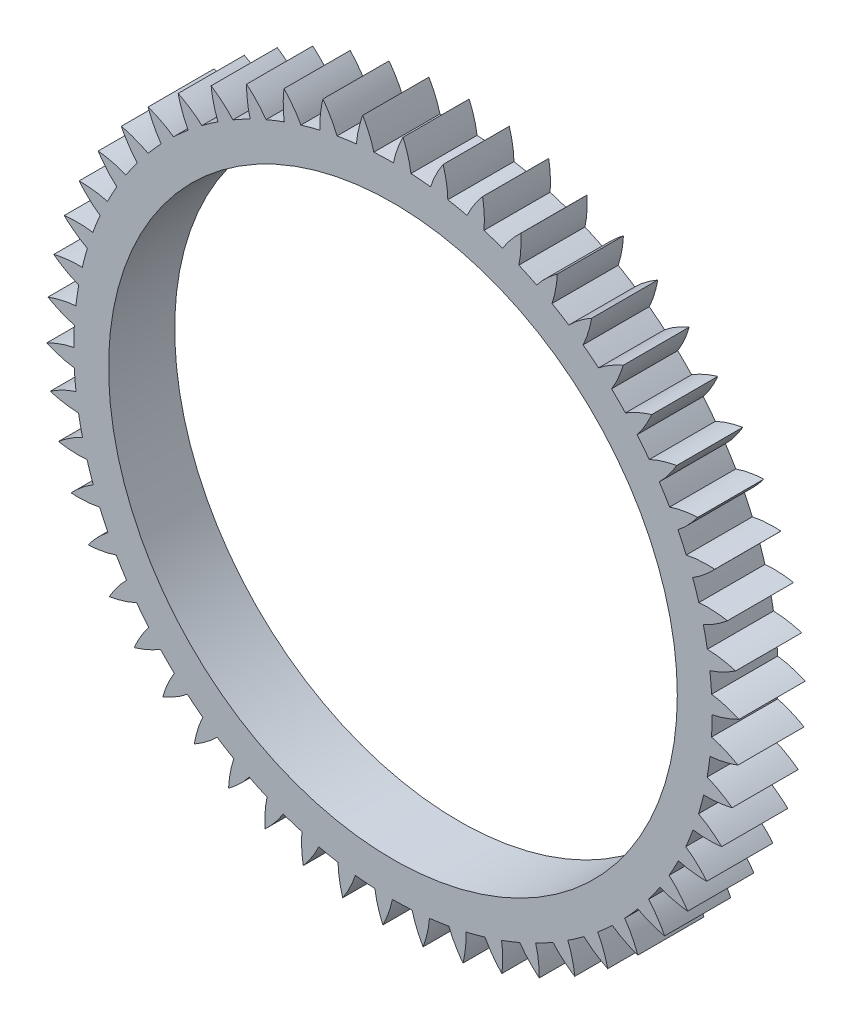
SolidWorks part; units mm, degrees
ref_plane "Front Plane" through (0, 0, 0) normal (0, 0, 1) x (1, 0, 0)
ref_plane "Top Plane" through (0, 0, 0) normal (0, 1, 0) x (1, 0, 0)
ref_plane "Right Plane" through (0, 0, 0) normal (1, 0, 0) x (0, 0, -1)
sketch "Sketch1" plane through (0, 0, 0) normal (0, 0, 1) x (1, 0, 0)
  line L0 (0, 0) -> (52.4519, -1.5262) construction
  line L1 (0, 0) -> (52.4519, 1.5262) construction
  line L2 (0, 0) -> (52.4519, -1.5262) construction
  line L3 (0, 0) -> (52.4741, 0) construction
  line L4 (0, 0) -> (52.2744, 4.5734) construction
  line L5 (0, 0) -> (52.4519, 1.5262)
  line L6 (48.237, -1.4036) -> (42.9818, -1.2506)
  circle A0 centre (0, 0) radius 50.6 construction
  circle A1 centre (0, 0) radius 48.2574 construction
  circle A2 centre (0, 0) radius 47.5484 construction
  circle A3 centre (0, 0) radius 52.4741 construction
  arc A4 (48.2533, 0.6333) -> (48.237, -1.4036) centre (0, 0) cw
  arc A5 (52.3753, 3.2182) -> (52.1207, -6.0799) centre (0, 0) cw
  arc A6 (42.9818, -1.2506) -> (42.9818, 1.2506) centre (0, 0) ccw
  spline S0 degree 4 poles (47.5484, 0) (47.6112, 0.0018) (47.7366, 0.009) (47.9743, 0.0351) (48.3224, 0.09) (48.9188, 0.2125) (49.8514, 0.4702) (51.0763, 0.915) (52.7294, 1.6795) (54.5797, 2.7428) (56.506, 4.0791) (58.4581, 5.6841) (60.2875, 7.4269) (61.9965, 9.2875) (63.6661, 11.3468) (65.5727, 14.0192) (67.5998, 17.3703) (69.6104, 21.4518) (71.4211, 26.1723) (72.8241, 31.0286) (73.8355, 35.9808) (74.3915, 40.3678) (74.6426, 44.1482) (74.7063, 47.304) (74.6718, 49.8289) (74.5535, 52.3511) (74.3534, 54.8684) (74.0032, 58.005) (73.5222, 61.1257) (72.9762, 63.9129) (72.4048, 66.3738) (72.0712, 67.6936) (71.8561, 68.5055) (71.6703, 69.1859) (71.4684, 69.9045) (71.2972, 70.4962) (70.9615, 71.62) (70.6933, 72.4658) (70.3553, 73.5115) (70.0426, 74.4282) (69.6958, 75.4214) (69.3545, 76.3545) (69.08, 77.0882) (68.9003, 77.5524) (68.8066, 77.7942) knots 0 0 0 0 0 0.002802 0.005604 0.010661 0.015718 0.02996 0.048734 0.068727 0.096889 0.125051 0.153212 0.181374 0.209535 0.237696 0.271429 0.327752 0.384075 0.440398 0.496721 0.553044 0.609367 0.637529 0.66569 0.693852 0.722013 0.750174 0.778336 0.834659 0.86282 0.876901 0.890982 0.895509 0.900036 0.909091 0.920455 0.931818 0.943182 0.954545 0.965909 0.977273 0.988636 1 1 1 1 1 construction
  spline S1 degree 4 poles (47.5484, 0) (47.6112, 0.0018) (47.7366, 0.009) (47.9743, 0.0351) (48.3224, 0.09) (48.9188, 0.2125) (49.8514, 0.4702) (51.0763, 0.915) (52.7294, 1.6795) (54.5797, 2.7428) (56.506, 4.0791) (58.4581, 5.6841) (60.2875, 7.4269) (61.9965, 9.2875) (63.6661, 11.3468) (65.5727, 14.0192) (67.5998, 17.3703) (69.6104, 21.4518) (71.4211, 26.1723) (72.8241, 31.0286) (73.8355, 35.9808) (74.3915, 40.3678) (74.6426, 44.1482) (74.7063, 47.304) (74.6718, 49.8289) (74.5535, 52.3511) (74.3534, 54.8684) (74.0032, 58.005) (73.5222, 61.1257) (72.9762, 63.9129) (72.4048, 66.3738) (72.0712, 67.6936) (71.8561, 68.5055) (71.6703, 69.1859) (71.5463, 69.6274) (71.469, 69.8988) (71.4179, 70.076) knots 0 0 0 0 0 0.002802 0.005604 0.010661 0.015718 0.02996 0.048734 0.068727 0.096889 0.125051 0.153212 0.181374 0.209535 0.237696 0.271429 0.327752 0.384075 0.440398 0.496721 0.553044 0.609367 0.637529 0.66569 0.693852 0.722013 0.750174 0.778336 0.834659 0.86282 0.876901 0.890982 0.895509 0.900036 0.909091 0.909091 0.909091 0.909091 0.909091
  dimension "pitchRadius" = 50.6
  dimension "addendumRadius" = 52.4741
  dimension "dedendumRadius" = 48.2574
  dimension "baseRadius" = 47.5484
  dimension "D1" = 3.333
  dimension "D2" = 1.667
  dimension "toothArc" = 6.667
  dimension "D3" = 43
extrude "Boss-Extrude1" add sketch "Sketch1" along normal blind 10 contours S1 A5 L5 A6 L6 A4 region at (46.4133, 0.1773, 0)
mirror "Mirror1" about plane through (0, 0, 10) normal (-0.0291, 0.9996, 0) of "Boss-Extrude1"
pattern_circular "CirPattern2" count 54 over 360 about axis through (0, 0, 10) along (0, 0, -1) of "Mirror1", "Boss-Extrude1"
equation "\"D1@Sketch1\"=\"toothArc@Sketch1\"/2"
equation "\"D2@Sketch1\"=\"toothArc@Sketch1\"/4"
equation "\"pitchRadius\"= 5.06"
equation "\"nTeeth\"= 54"
equation "\"pressureAngle\"= 20"
equation "\"baseRadius\"= \"pitchRadius\" * cos ( \"pressureAngle\" )"
equation "\"diametralPitch\"= \"nTeeth\" / ( 2 * \"pitchRadius\" )'note units: cm^-1"
equation "\"dedendum\"= 1.25 / \"diametralPitch\"'for full depth, 20 deg pressure angle"
equation "\"addendum\"= 1 / \"diametralPitch\""
equation "\"pitchRadius@Sketch1\"= \"pitchRadius\""
equation "\"addendumRadius@Sketch1\"= \"pitchRadius\" + \"addendum\""
equation "\"dedendumRadius@Sketch1\"= \"pitchRadius\" - \"dedendum\""
equation "\"baseRadius@Sketch1\"= \"baseRadius\""
equation "\"toothArc@Sketch1\"=360/\"nTeeth\""
